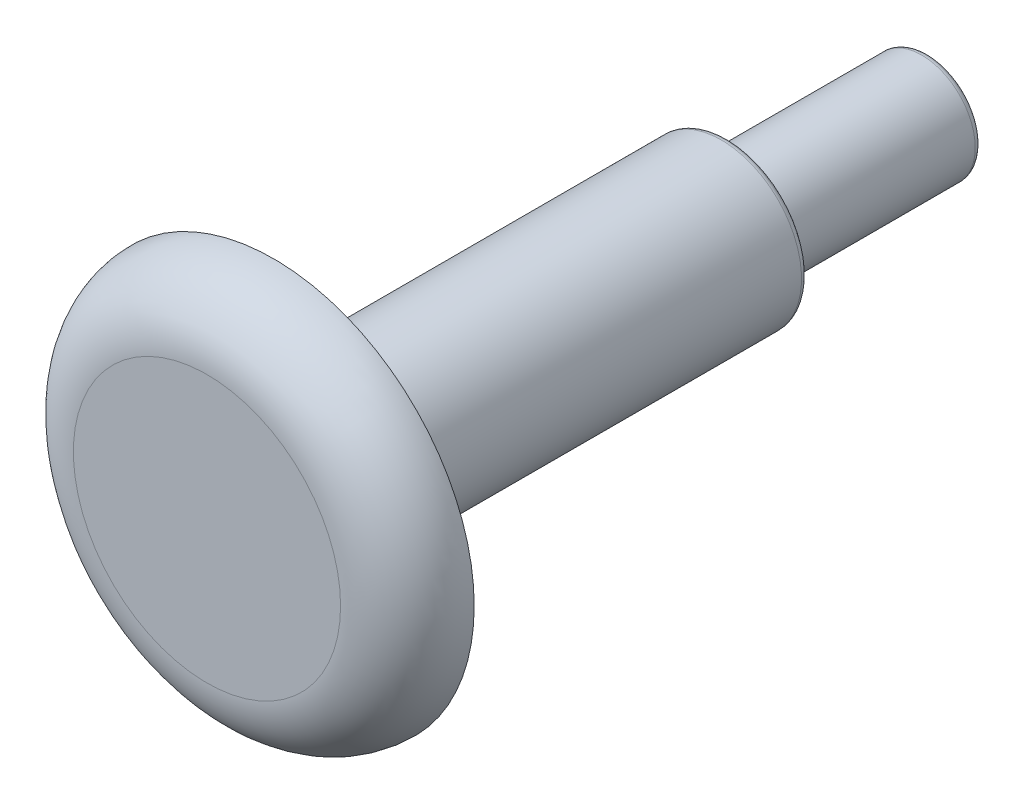
SolidWorks part; units mm, degrees
material "Plastique personnalisé"
ref_plane "Plan de face" through (0, 0, 0) normal (0, 0, 1) x (1, 0, 0)
ref_plane "Plan de dessus" through (0, 0, 0) normal (0, 1, 0) x (1, 0, 0)
ref_plane "Plan de droite" through (0, 0, 0) normal (1, 0, 0) x (0, 0, -1)
sketch "Esquisse1" plane through (0, 0, 0) normal (0, 0, 1) x (1, 0, 0)
  circle A0 centre (0, 0) radius 6
extrude "Boss.-Extru.1" add sketch "Esquisse1" along normal blind 49
sketch "Esquisse2" plane through (0, 0, 49) normal (0, 0, 1) x (1, 0, 0)
  circle A0 centre (0, 0.0468) radius 15
extrude "Boss.-Extru.2" add sketch "Esquisse2" along normal blind 5
fillet "Congé1" radius 5 1 edges at (15, 0.0468, 54)
sketch "Esquisse3" plane through (0, 0, 0) normal (0, 0, -1) x (-1, 0, 0)
  circle A0 centre (0, 0) radius 4
  circle A1 centre (0, 0) radius 6
extrude "Enlèv. mat.-Extru.1" cut sketch "Esquisse3" against normal blind 15
fillet "Congé3" radius 0.5 1 edges at (-4, 0, 0)
fillet "Congé4" radius 0.5 1 edges at (-6, 0, 15)
